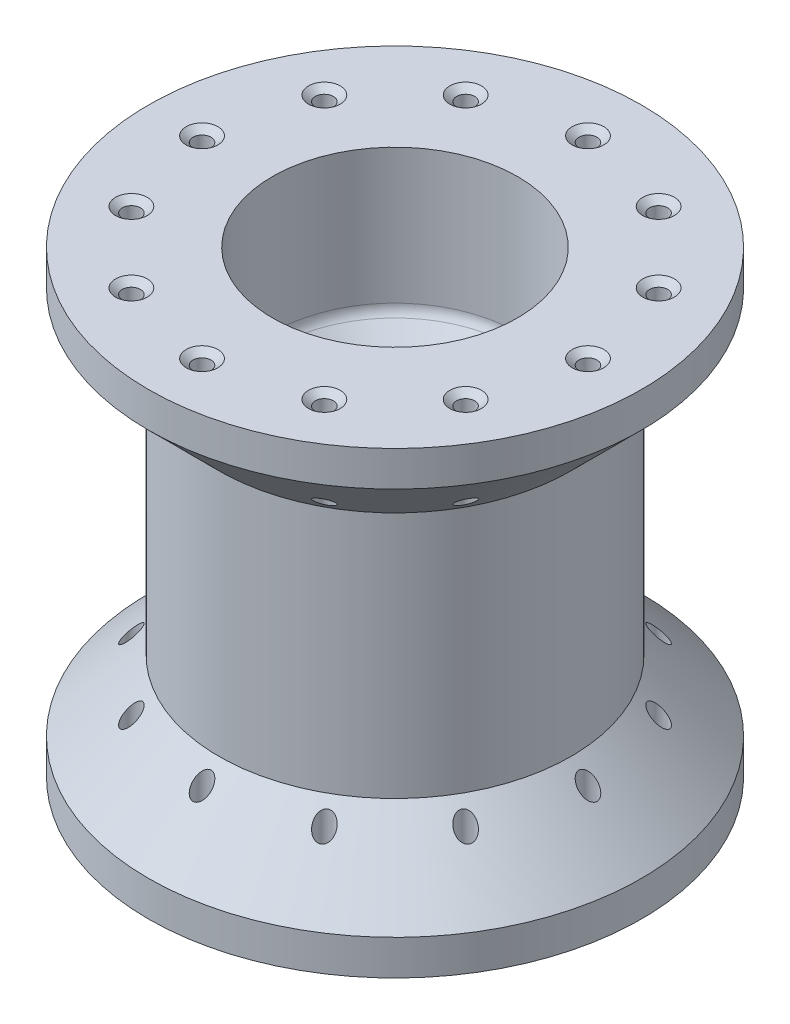
SolidWorks part; units mm, degrees
ref_plane "Front Plane" through (0, 0, 0) normal (0, 0, 1) x (1, 0, 0)
ref_plane "Top Plane" through (0, 0, 0) normal (0, 1, 0) x (1, 0, 0)
ref_plane "Right Plane" through (0, 0, 0) normal (1, 0, 0) x (0, 0, -1)
sketch "Sketch1" plane through (0, 0, 0) normal (1, 0, 0) x (0, 0, -1)
  line L8 (31.75, 82.7) -> (44.45, 82.7)
  line L9 (44.45, 82.7) -> (44.45, 76.35)
  line L10 (44.45, 76.35) -> (31.75, 76.35) construction
  line L11 (31.75, 0) -> (44.45, 0)
  line L12 (44.45, 0) -> (44.45, 6.35)
  line L13 (44.45, 6.35) -> (31.75, 6.35) construction
  line L27 (22.1, 76.35) -> (22.1, 82.7)
  line L28 (22.1, 82.7) -> (31.75, 82.7)
  line L29 (22.1, 6.35) -> (22.1, 0)
  line L30 (22.1, 0) -> (31.75, 0)
  line L31 (22.1, 76.35) -> (22.1, 6.35)
  line L32 (22.1, 0) -> (0, 0) construction
  line L33 (0, 0) -> (0, 6.35) construction
  line L34 (44.45, 6.35) -> (31.75, 19.05)
  line L35 (44.45, 76.35) -> (31.75, 63.65)
  line L36 (31.75, 63.65) -> (31.75, 19.05)
  line L37 (31.75, 76.35) -> (31.75, 63.65) construction
  line L38 (31.75, 19.05) -> (31.75, 6.35) construction
  dimension "D1" = 6.35
  dimension "D2" = 6.35
  dimension "D3" = 12.7
  dimension "D4" = 12.7
  dimension "D7" = 70
  dimension "D8" = 22.1
  dimension "D5" = 17.9605
  dimension "D6" = 17.9605
revolve "Chamber" add sketch "Sketch1" angle 360 about L33
sketch "Sketch4" plane through (0, 0, 0) normal (1, 0, 0) x (0, 0, -1)
  line L0 (0, 0) -> (0, 82.7) construction
  line L1 (22.1, 82.7) -> (-22.1, 82.7) construction
  line L8 (0, 41.35) -> (22.1, 41.35) construction
  line L15 (0, 0) -> (22.1, 0) construction
  line L16 (22.1, 0) -> (22.1, 48.6279) construction
  line L17 (22.1, 57.3) -> (6.63, 57.3) construction
  line L18 (6.63, 57.3) -> (6.63, 41.83) construction
  line L23 (21.3561, 56.5561) -> (7.002, 42.202)
  line L24 (6.63, 41.3039) -> (6.63, 39.9032)
  line L25 (7.0636, 39.7236) -> (17.7639, 50.4239)
  line L26 (22.1, 58.3521) -> (22.1, 82.7) construction
  line L27 (0, 82.7) -> (22.1, 82.7) construction
  line L29 (22.1, 58.3521) -> (22.1, 48.6279)
  arc A0 (22.1, 48.6279) -> (17.7639, 50.4239) centre (19.56, 48.6279) ccw
  arc A1 (22.1, 58.3521) -> (21.3561, 56.5561) centre (19.56, 58.3521) cw
  arc A2 (7.002, 42.202) -> (6.63, 41.3039) centre (7.9, 41.3039) ccw
  arc A3 (6.63, 39.9032) -> (7.0636, 39.7236) centre (6.884, 39.9032) ccw
  point P24 (6.63, 39.29)
  point P25 (25.4743, 106.7645)
  point P26 (25.4, 139.7)
  point P28 (25.4, 139.7)
  point P29 (25.4, 139.7)
  point P30 (25.4, 139.7)
  point P31 (25.4, 115.3521)
  dimension "D5" = 2.54
  dimension "D6" = 2.54
  dimension "D7" = 1.27
  dimension "D8" = 0.254
  dimension "D2" = 22.1
  dimension "D1" = 6.63
  dimension "D3" = 25.4
  dimension "D4" = 2.54
revolve "Turbulence Rings" add sketch "Sketch4" angle 360 about L0
sketch "Sketch5" plane through (0, 82.7, 0) normal (0, 1, 0) x (1, 0, 0)
  line L0 (0, 0) -> (-34.8, 0) construction
  line L1 (0, 0) -> (-30.1377, 17.4) construction
  circle A0 centre (0, 0) radius 34.8 construction
  point P0 (0, 0)
  point P5 (-34.8, 0)
  point P9 (-30.1377, 17.4)
  point P10 (-17.4, 30.1377)
  point P11 (0, 34.8)
  point P12 (17.4, 30.1377)
  point P13 (30.1377, 17.4)
  point P14 (34.8, 0)
  point P15 (30.1377, -17.4)
  point P16 (17.4, -30.1377)
  point P17 (0, -34.8)
  point P18 (-17.4, -30.1377)
  point P19 (-30.1377, -17.4)
  point P20 (0, 0)
  point P21 (0, 0)
  point P24 (0, 0)
  point P26 (0, 0)
  dimension "D3" = 34.8
  dimension "D1" = 30
  dimension "D2" = 12
hole_wizard "CSK for #4 Flat Head Machine Screw (100)2" positions "Sketch5" profile "Sketch15" countersink size "#4" standard "ANSI Inch" end condition through all
sketch "Sketch15" plane through (0, 82.7, 0) normal (1, 0, 0) x (0, 0, 1)
  line L0 (0, 0) -> (0, 82.7)
  line L1 (0, 82.7) -> (2.2669, 82.7)
  line L2 (1.6319, 82.065) -> (1.6319, 1.0284)
  line L3 (1.6319, 1.0284) -> (2.8575, 0)
  line L5 (2.8575, 0) -> (0, 0)
  line L6 (-1.6319, 1.0284) -> (-2.8575, 0) construction
  line L7 (2.2669, 82.7) -> (1.6319, 82.065)
  line L8 (-2.267, 82.7) -> (-1.632, 82.065) construction
  line L11 (0, -6.35) -> (0, 107.95) construction
  dimension "Thru Hole Dia." = 3.2639
  dimension "Thru Hole Depth" = 82.7
  dimension "Near C'Sink Dia." = 5.715
  dimension "Near C'Sink Angle" = 100
  dimension "Far C'Sink Dia." = 4.5339
  dimension "Far C'Sink Angle" = 90
equation "\"Thickness of Material\"= 0.3in"
equation "\"Chamber Length\" = 7cm"
equation "\"Flange Length\"= 0.5in"
equation "\"Chamber Wall Thickness\"= 0.25in"
equation "\"Ring Length\"= 1.2in"
equation "\"Ring Thickness\"= 0.1in"
equation "\"Number of Rings\"= 2"
equation "\"Chamber Radius\"= 4.42cm / 2"
equation "\"D7@Sketch1\"= \"Chamber Length\""
equation "\"D8@Sketch1\"= \"Chamber Radius\""
equation "\"Flange Thickness\"= 0.25in"
equation "\"D1@Sketch1\"= \"Flange Thickness\""
equation "\"D3@Sketch5\"= \"Chamber Radius\" + \"Chamber Wall Thickness\" + ( \"Flange to Inner Wall Length\" / 2 )"
equation "\"Flange to Inner Wall Length\"= ( \"Chamber Radius\" + \"Chamber Wall Thickness\" + \"Flange Length\" ) - ( \"Chamber Radius\" + \"Chamber Wall Thickness\" )"
equation "\"D2@Sketch4\"= \"Chamber Radius\""
equation "\"Turbulence Ring Distance from Top\"= 1in"
equation "\"D4@Sketch1\"= \"Flange Length\""
equation "\"D3@Sketch1\"= \"Flange Length\""
equation "\"Center to Ring Edge Distance\"= 0.3 * ( \"Chamber Radius\" )"
equation "\"D1@Sketch4\"= \"Center to Ring Edge Distance\""
equation "\"D3@Sketch4\"= \"Turbulence Ring Distance from Top\""
equation "\"D4@Sketch4\"= \"Ring Thickness\""
equation "\"Flange Chamfer\"= sqr ( \"Flange Length\" )"
equation "\"D5@Sketch1\"= \"Flange Chamfer\""
equation "\"D6@Sketch1\"= \"Flange Chamfer\""
